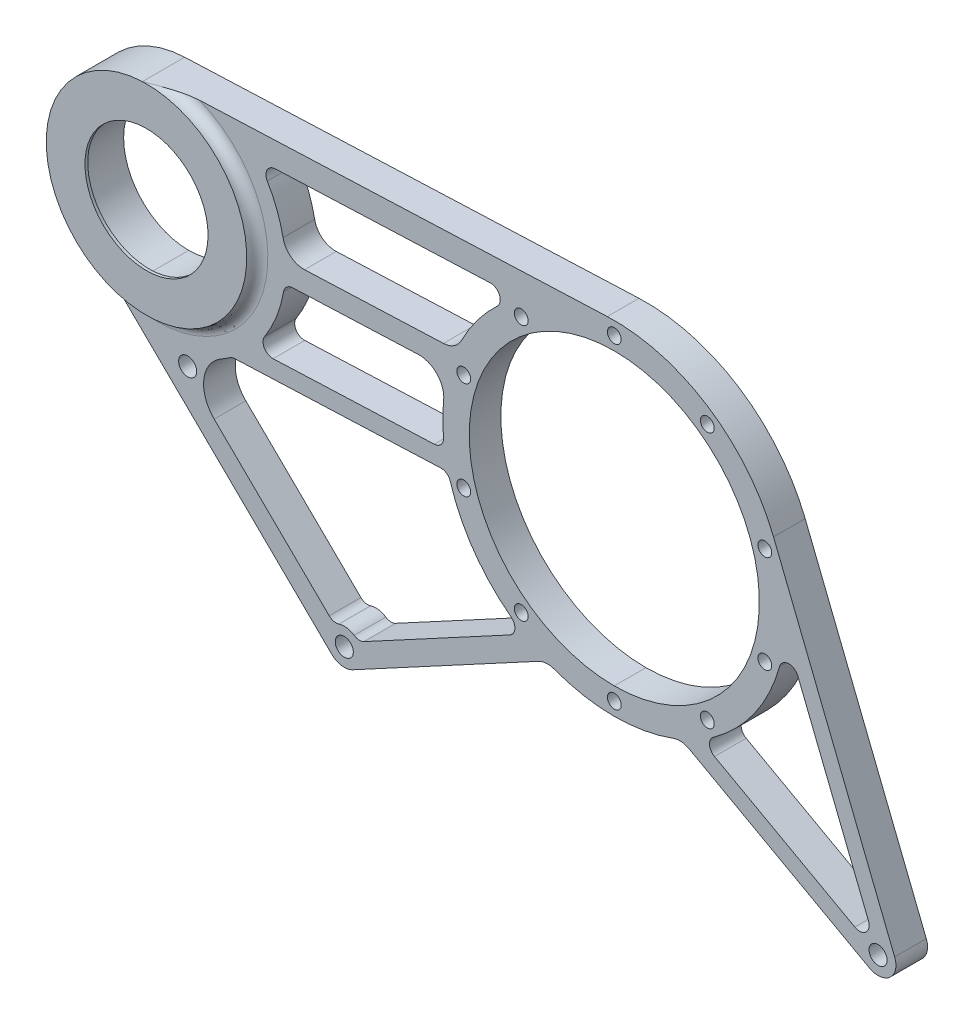
SolidWorks part; units mm, degrees
material "6061-T6 (SS)"
ref_plane "Front Plane" through (0, 0, 0) normal (0, 0, 1) x (1, 0, 0)
ref_plane "Top Plane" through (0, 0, 0) normal (0, 1, 0) x (1, 0, 0)
ref_plane "Right Plane" through (0, 0, 0) normal (1, 0, 0) x (0, 0, -1)
sketch "Sketch1" plane through (0, 0, 0) normal (0, 0, 1) x (1, 0, 0)
  line L0 (-114.3, 95.25) -> (-114.3, 107.95) construction
  line L1 (-280.8642, 163.1704) -> (-116.8043, 169.8118)
  line L2 (-304.7421, 101.1501) -> (-216.3071, 14.4521)
  line L3 (-13.0706, 21.4387) -> (-56.8054, 130.918)
  line L4 (-208.742, 13.3833) -> (-141.7118, 49.5504)
  line L5 (-22.1639, 13.4141) -> (-87.2342, 49.3665)
  circle A0 centre (-279.4, 127) radius 23.5
  circle A1 centre (-114.3, 95.25) radius 36 construction
  circle A2 centre (0, 0) radius 12.7 construction
  circle A3 centre (-228.6, 0) radius 12.7 construction
  circle A4 centre (-114.3, 107.95) radius 52.3875
  circle A5 centre (-19.05, 19.05) radius 3.2639
  circle A6 centre (-211.7995, 19.05) radius 3.2639
  circle A7 centre (-279.4, 127) radius 36.2
  arc A8 (-135.9521, 49.947) -> (-93.0137, 49.8118) centre (-114.3, 107.95) ccw
  arc A9 (-216.3071, 14.4521) -> (-208.742, 13.3833) centre (-211.7995, 19.05) ccw
  arc A10 (-22.1639, 13.4141) -> (-13.0706, 21.4387) centre (-19.05, 19.05) ccw
  arc A11 (-56.8054, 130.918) -> (-116.8043, 169.8118) centre (-114.3, 107.95) ccw
  arc A12 (-135.9521, 49.947) -> (-141.7118, 49.5504) centre (-138.3949, 43.4031) ccw
  arc A13 (-87.2342, 49.3665) -> (-93.0137, 49.8118) centre (-90.6122, 43.2526) ccw
  dimension "D5" = 72
  dimension "D6" = 47
  dimension "D7" = 25.4
  dimension "D8" = 25.4
  dimension "D11" = 104.775
  dimension "D14" = 6.5278
  dimension "D15" = 6.5278
  dimension "D16" = 25.4
  dimension "D17" = 12.7
  dimension "D18" = 123.825
  dimension "D19" = 3.175
  dimension "D20" = 6.985
  dimension "D21" = 6.985
  dimension "D1" = 114.3
  dimension "D2" = 95.25
  dimension "D3" = 279.4
  dimension "D4" = 127
  dimension "D9" = 228.6
  dimension "D10" = 12.7
  dimension "D12" = 19.05
  dimension "D13" = 19.05
extrude "Boss-Extrude1" add sketch "Sketch1" along normal blind 11.43 contours A13 L5 A10 L3 A11 L1 A7 L2 A9 L4 A12 A8 A6 A5 A4 | A7 A0 region at (-168.693, 91.0379, 0) region at (-255.035, 152.3713, 0)
sketch "Sketch2" plane through (0, 0, 11.43) normal (0, 0, 1) x (1, 0, 0)
  circle A0 centre (-279.4, 127) radius 36.2
  circle A1 centre (-279.4, 127) radius 23.5
extrude "Boss-Extrude2" add sketch "Sketch2" along normal blind 3.81
fillet "Fillet1" radius 3.81 1 edges at (-245.6173, 113.9936, 11.43)
sketch "Sketch3" plane through (0, 0, 11.43) normal (0, 0, 1) x (1, 0, 0)
  line L0 (-114.3, 107.95) -> (-114.3, 165.1) construction
  circle A0 centre (-114.3, 107.95) radius 57.15 construction
  circle A1 centre (-114.3, 165.1) radius 2.5
  circle A2 centre (-80.7081, 154.1853) radius 2.5
  circle A3 centre (-59.9471, 125.6103) radius 2.5
  circle A4 centre (-59.9471, 90.2897) radius 2.5
  circle A5 centre (-80.7081, 61.7147) radius 2.5
  circle A6 centre (-114.3, 50.8) radius 2.5
  circle A7 centre (-147.8919, 61.7147) radius 2.5
  circle A8 centre (-168.6529, 90.2897) radius 2.5
  circle A9 centre (-168.6529, 125.6103) radius 2.5
  circle A10 centre (-147.8919, 154.1853) radius 2.5
  point P25 (-114.3, 107.95)
  dimension "D1" = 114.3
  dimension "D2" = 5
  dimension "D3" = 10
extrude "5mm Holes" cut sketch "Sketch3" against normal through all
sketch "Sketch4" plane through (0, 0, 15.24) normal (0, 0, 1) x (1, 0, 0)
  circle A0 centre (-279.4, 127) radius 22.225
  circle A1 centre (-279.4, 127) radius 23.5 construction
  circle A2 centre (-279.4, 127) radius 23.5
  dimension "D1" = 44.45
extrude "Boss-Extrude3" add sketch "Sketch4" against normal blind 1
sketch "Sketch5" plane through (0, 0, 11.43) normal (0, 0, 1) x (1, 0, 0)
  line L0 (-48.0193, 91.8071) -> (-22.5033, 27.9342)
  line L1 (-13.0706, 21.4387) -> (-56.8054, 130.918) construction
  line L2 (-78.1047, 51.5771) -> (-27.4356, 23.5816)
  line L3 (-22.1639, 13.4141) -> (-87.2342, 49.3665) construction
  line L4 (-236.7455, 156.0591) -> (-159.125, 159.2013)
  line L5 (-263.8382, 163.8596) -> (-116.8043, 169.8118) construction
  line L6 (-226.1253, 129.7972) -> (-175.9845, 131.827)
  line L7 (-230.4174, 121.9972) -> (-185.1154, 123.8311)
  line L8 (-258.7869, 66.7686) -> (-217.2302, 26.028)
  line L9 (-204.6483, 24.2506) -> (-152.0143, 52.6499)
  line L10 (-292.5742, 89.2212) -> (-216.3071, 14.4521) construction
  line L11 (-208.742, 13.3833) -> (-141.7118, 49.5504) construction
  line L12 (-237.4937, 96.2899) -> (-179.3047, 98.6455)
  line L13 (-251.3498, 89.3738) -> (-177.0086, 92.3833)
  arc A0 (-175.0426, 119.9291) -> (-175.9673, 102.4457) centre (-114.3, 107.95) ccw construction
  circle A1 centre (-211.7995, 19.05) radius 6.4389 construction
  circle A2 centre (-19.05, 19.05) radius 6.4389 construction
  arc A3 (-54.6287, 91.4427) -> (-78.4387, 57.481) centre (-114.3, 107.95) cw
  arc A4 (-48.0193, 91.8071) -> (-54.6287, 91.4427) centre (-51.2626, 90.5115) ccw
  arc A5 (-27.4356, 23.5816) -> (-22.5033, 27.9342) centre (-25.7466, 26.6385) ccw
  arc A6 (-78.1047, 51.5771) -> (-78.4387, 57.481) centre (-76.4157, 54.634) cw
  arc A7 (-233.9104, 135.9413) -> (-239.6024, 150.7781) centre (-279.4, 127) ccw construction
  arc A8 (-292.5742, 89.2212) -> (-263.8382, 163.8596) centre (-279.4, 127) ccw construction
  arc A9 (-213.7352, 25.191) -> (-208.2383, 24.4145) centre (-211.7995, 19.05) cw
  arc A10 (-156.5977, 153.1613) -> (-169.499, 135.9897) centre (-114.3, 107.95) ccw
  arc A11 (-175.9093, 114.0697) -> (-175.9673, 102.4457) centre (-114.3, 107.95) ccw
  arc A12 (-173.5263, 89.9112) -> (-151.5703, 58.5123) centre (-114.3, 107.95) ccw
  arc A13 (-239.6024, 150.7781) -> (-233.9104, 135.9413) centre (-279.4, 127) cw
  arc A14 (-233.7176, 119.1025) -> (-240.5609, 101.6865) centre (-279.4, 127) cw
  arc A15 (-240.5609, 101.6865) -> (-233.7176, 119.1025) centre (-279.4, 127) ccw construction
  arc A16 (-253.1835, 88.7646) -> (-256.2406, 86.8392) centre (-279.4, 127) cw
  arc A17 (-159.125, 159.2013) -> (-156.5977, 153.1613) centre (-158.9837, 155.7117) cw
  arc A20 (-236.7455, 156.0591) -> (-239.6024, 150.7781) centre (-236.6043, 152.5695) ccw
  arc A21 (-179.3047, 98.6455) -> (-175.9673, 102.4457) centre (-179.446, 102.1352) ccw
  arc A23 (-230.4174, 121.9972) -> (-233.7176, 119.1025) centre (-230.2762, 118.5075) ccw
  arc A24 (-237.4937, 96.2899) -> (-240.5609, 101.6865) centre (-237.6349, 99.7796) cw
  arc A25 (-217.2302, 26.028) -> (-213.7352, 25.191) centre (-214.7852, 28.522) ccw
  arc A26 (-204.6483, 24.2506) -> (-208.2383, 24.4145) centre (-206.3067, 27.3242) cw
  arc A27 (-152.0143, 52.6499) -> (-151.5703, 58.5123) centre (-153.6727, 55.7236) ccw
  arc A28 (-177.0086, 92.3833) -> (-173.5263, 89.9112) centre (-176.8673, 88.8936) cw
  arc A29 (-251.3498, 89.3738) -> (-253.1835, 88.7646) centre (-251.2085, 85.8842) ccw
  arc A31 (-173.5263, 89.9112) -> (-170.4887, 133.9499) centre (-114.3, 107.95) ccw construction
  arc A32 (-273.3418, 81.0375) -> (-253.1835, 88.7646) centre (-279.4, 127) ccw construction
  arc A33 (-258.7869, 66.7686) -> (-256.2406, 86.8392) centre (-249.8962, 75.8374) cw
  arc A34 (-169.499, 135.9897) -> (-175.9845, 131.827) centre (-176.2928, 139.4407) cw
  arc A35 (-233.9104, 135.9413) -> (-226.1253, 129.7972) centre (-226.4335, 137.411) ccw
  arc A36 (-185.1154, 123.8311) -> (-175.9093, 114.0697) centre (-184.7558, 114.9484) cw
  point P17 (-52.5701, 103.1988)
  point P23 (-83.2204, 54.4036)
  point P51 (-148.3837, 159.6362)
  point P54 (-171.3442, 132.0148)
  point P60 (-243.0732, 155.8029)
  point P63 (-175.5324, 98.7982)
  point P66 (-174.02, 124.2803)
  point P75 (-215.4925, 24.3245)
  point P78 (-206.7898, 23.0951)
  point P81 (-146.981, 55.3657)
  point P84 (-174.2524, 92.4948)
  point P90 (-273.3418, 81.0375)
  dimension "D1" = 123.825
  dimension "D2" = 12.8778
  dimension "D5" = 3.4925
  dimension "D6" = 6.35
  dimension "D14" = 3.4925
  dimension "D15" = 12.7
  dimension "D16" = 7.62
  dimension "D17" = 7.62
  dimension "D18" = 8.89
  dimension "D3" = 6.35
  dimension "D4" = 6.35
  dimension "D7" = 8.89
  dimension "D8" = 7.62
  dimension "D9" = 7.62
  dimension "D10" = 7.62
  dimension "D11" = 6.35
  dimension "D12" = 25.4
  dimension "D13" = 26.67
extrude "Cut-Extrude2" cut sketch "Sketch5" against normal through all both and the other way through all
ref_axis "Axis2" through (-279.4, 127, 14.24) along (0, 0, -1)
ref_axis "Axis1" through (-114.3, 107.95, 11.43) along (0, 0, -1)
ref_plane "Plane1" through (-114.3, 0, 0) normal (1, 0, 0) x (0, 0, -1)
ref_plane "Plane2" through (-279.4, 0, 0) normal (1, 0, 0) x (0, 0, -1)
ref_plane "Plane3" through (0, 0, 5.715) normal (0, 0, -1) x (-1, 0, 0)
ref_plane "Plane4" through (0, 0, 7.12) normal (0, 0, -1) x (-1, 0, 0)
split line "Split Line1"
split line "Split Line2"
sketch "Sketch6" plane through (0, 0, 5.715) normal (0, 0, -1) x (-1, 0, 0)
  circle A1 centre (114.3, 107.95) radius 52.3875 construction
sketch "Sketch7" plane through (0, 0, 7.12) normal (0, 0, -1) x (-1, 0, 0)
  circle A0 centre (279.4, 127) radius 23.5
sketch "Sketch8" plane through (0, 0, 11.43) normal (0, 0, 1) x (1, 0, 0)
  circle A0 centre (-268.3542, 78.4783) radius 3.2639
extrude "Cut-Extrude3" cut sketch "Sketch8" against normal through all both and the other way through all
ref_point "Puck Center"
ref_point "Bearing Center"
sketch "Sketch9" plane through (0, 0, 0) normal (0, 0, 1) x (1, 0, 0)
  line L0 (-210.8988, 25.4256) -> (-210.8988, 91.0113) construction
  line L1 (-177.0086, 92.3833) -> (-251.3498, 89.3738) construction
  line L2 (-236.1159, 143.6054) -> (-163.7987, 145.1392) construction
  circle A0 centre (-114.3, 107.95) radius 31.75 construction
  arc A1 (-208.2383, 24.4145) -> (-213.7352, 25.191) centre (-211.7995, 19.05) ccw construction
  circle A2 centre (-210.8988, 77.2346) radius 5.08
  circle A3 centre (-210.8988, 45.0623) radius 5.08
  circle A4 centre (-146.05, 107.95) radius 5.08
  circle A5 centre (-114.3, 139.7) radius 5.08
  circle A6 centre (-82.55, 107.95) radius 5.08
  circle A7 centre (-114.3, 76.2) radius 5.08
  arc A8 (-233.9104, 135.9413) -> (-239.6024, 150.7781) centre (-279.4, 127) ccw construction
  arc A9 (-156.5977, 153.1613) -> (-169.499, 135.9897) centre (-114.3, 107.95) ccw construction
  circle A10 centre (-199.9573, 144.3723) radius 5.08
  point P0 (-48.5383, 56.2255)
  point P8 (-146.05, 107.95)
  point P30 (-114.3, 107.95)
  dimension "D1" = 63.5
  dimension "D2" = 10.16
  dimension "D3" = 10.16
  dimension "D4" = 10.16
  dimension "D6" = 10.16
  dimension "D5" = 4
sketch "Sketch10" plane through (0, 0, 0) normal (0, 0, -1) x (-1, 0, 0)
  line L0 (202.0088, 77.2346) -> (202.0088, 45.0623)
  line L1 (219.7888, 77.2346) -> (219.7888, 45.0623)
  circle A0 centre (114.3, 107.95) radius 38.1
  circle A1 centre (199.9573, 144.3723) radius 8.89
  circle A2 centre (199.9573, 144.3723) radius 5.08
  circle A3 centre (199.9573, 144.3723) radius 5.08 construction
  circle A4 centre (146.05, 107.95) radius 5.08
  circle A5 centre (146.05, 107.95) radius 5.08 construction
  circle A6 centre (210.8988, 45.0623) radius 5.08
  circle A7 centre (210.8988, 45.0623) radius 5.08 construction
  circle A8 centre (210.8988, 77.2346) radius 5.08
  circle A9 centre (210.8988, 77.2346) radius 5.08 construction
  circle A10 centre (114.3, 76.2) radius 5.08
  circle A11 centre (114.3, 76.2) radius 5.08 construction
  circle A12 centre (82.55, 107.95) radius 5.08
  circle A13 centre (82.55, 107.95) radius 5.08 construction
  circle A14 centre (114.3, 139.7) radius 5.08
  circle A15 centre (114.3, 139.7) radius 5.08 construction
  arc A16 (219.7888, 77.2346) -> (202.0088, 77.2346) centre (210.8988, 77.2346) ccw
  arc A17 (202.0088, 45.0623) -> (219.7888, 45.0623) centre (210.8988, 45.0623) ccw
  circle A18 centre (210.8988, 45.0623) radius 8.89 construction
  circle A19 centre (210.8988, 77.2346) radius 8.89 construction
  point P26 (0, 0)
  dimension "D1" = 76.2
  dimension "D9" = 3.81
  dimension "D2" = 0
  dimension "D3" = 0
  dimension "D4" = 0
  dimension "D5" = 0
  dimension "D6" = 0
  dimension "D7" = 0
  dimension "D8" = 0
  dimension "D10" = 3.81
